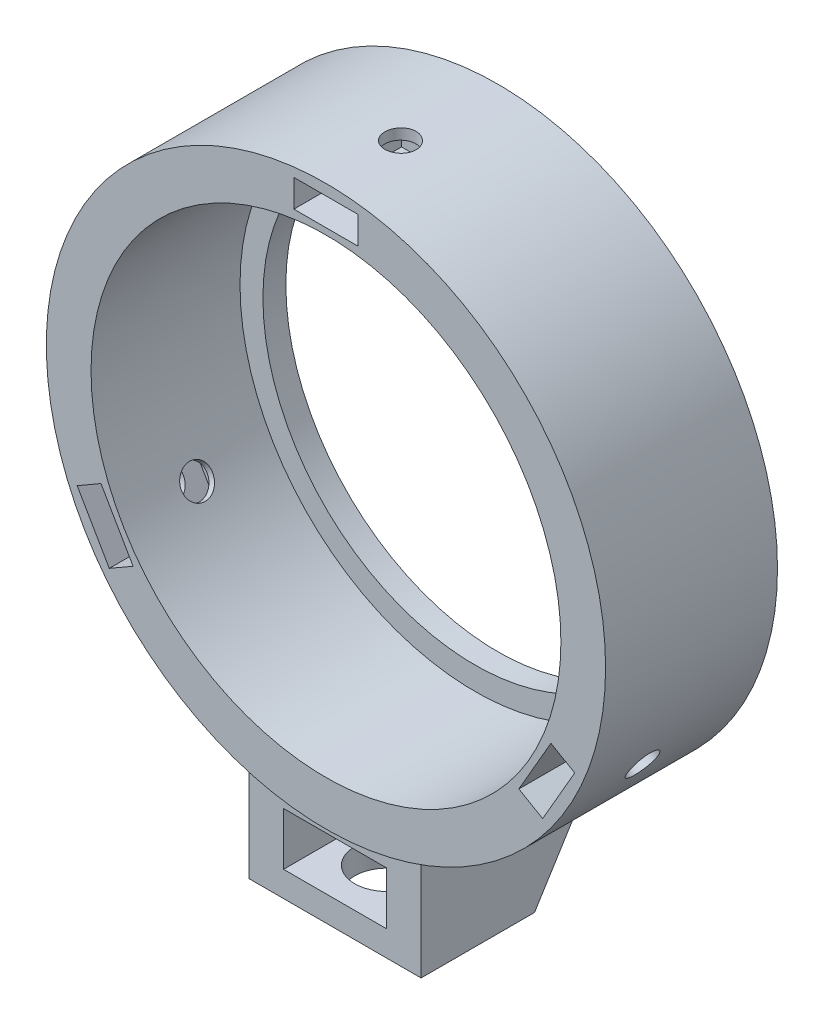
SolidWorks part; units mm, degrees
ref_plane "Front Plane" through (0, 0, 0) normal (0, 0, 1) x (1, 0, 0)
ref_plane "Top Plane" through (0, 0, 0) normal (0, 1, 0) x (1, 0, 0)
ref_plane "Right Plane" through (0, 0, 0) normal (1, 0, 0) x (0, 0, -1)
sketch "Sketch1" plane through (0, 0, 0) normal (0, 0, 1) x (1, 0, 0)
  circle A0 centre (0, 0) radius 30.988
  dimension "D1" = 61.976
extrude "Boss-Extrude1" add sketch "Sketch1" along normal blind 19.05
sketch "Sketch2" plane through (0, 0, 19.05) normal (0, 0, 1) x (1, 0, 0)
  circle A0 centre (0, 0) radius 26.035
  dimension "D1" = 52.07
extrude "Cut-Extrude1" cut sketch "Sketch2" against normal through all
sketch "Sketch4" plane through (0, 0, 0) normal (0, 0, -1) x (-1, 0, 0)
  circle A0 centre (0, 0) radius 26.035
  circle A1 centre (0, 0) radius 23.495
  circle A2 centre (0, 0) radius 26.035 construction
  dimension "D1" = 2.54
  dimension "D2" = 0
extrude "Boss-Extrude2" add sketch "Sketch4" against normal blind 2.54
sketch "Sketch11" plane through (0, 0, 19.05) normal (0, 0, 1) x (1, 0, 0)
  line L1 (-3.556, 26.7335) -> (3.556, 26.7335)
  line L2 (-3.556, 26.7335) -> (-3.556, 29.7815)
  line L3 (-3.556, 29.7815) -> (3.556, 29.7815)
  line L4 (3.556, 26.7335) -> (3.556, 29.7815)
  line L5 (-3.556, 26.7335) -> (3.556, 29.7815) construction
  line L6 (-3.556, 29.7815) -> (3.556, 26.7335) construction
  point P0 (0, 28.2575)
  dimension "D1" = 3.048
  dimension "D2" = 7.112
  dimension "D3" = 28.2575
extrude "Cut-Extrude3" cut sketch "Sketch11" against normal blind 11.938
pattern_circular "CirPattern2" count 3 over 360 about axis through (0, 0, 19.05) along (0, 0, -1) of "Cut-Extrude3"
ref_plane "Plane5" through (0, 12.7, 0) normal (0, 1, 0) x (1, 0, 0)
hole_wizard "#4 Clearance Hole1" positions "Sketch13" profile "Sketch14" hole size "#4" standard "ANSI Inch" end condition through all
sketch "Sketch13" plane through (0, 12.7, 0) normal (0, 1, 0) x (1, 0, 0)
  line L0 (3.556, -19.05) -> (-3.556, -19.05) construction
  point P0 (0, -10.795)
  dimension "D1" = 8.255
sketch "Sketch14" plane through (0, 12.7, 10.795) normal (1, 0, 0) x (0, 0, -1)
  line L0 (0, 0) -> (0, 34.4564)
  line L1 (0, 34.4564) -> (1.7272, 34.4564)
  line L2 (1.7272, 34.4564) -> (1.7272, 0)
  line L5 (1.7272, 0) -> (0, 0)
  line L11 (0, -6.35) -> (0, 107.95) construction
  dimension "Thru Hole Dia." = 3.4544
  dimension "Thru Hole Depth" = 34.4564
ref_plane "Plane6" through (0, -27.94, 0) normal (0, 1, 0) x (1, 0, 0)
sketch "Sketch15" plane through (0, -27.94, 0) normal (0, 1, 0) x (1, 0, 0)
  line L0 (-30.988, -19.05) -> (30.988, -19.05) construction
  line L1 (-9.144, -0.762) -> (9.906, -0.762)
  line L2 (-9.144, -0.762) -> (-9.144, -18.415)
  line L3 (-9.144, -18.415) -> (9.906, -18.415)
  line L4 (9.906, -0.762) -> (9.906, -18.415)
  line L5 (3.556, -7.112) -> (3.556, -19.05) construction
  line L6 (-3.556, -7.112) -> (-3.556, -19.05) construction
  line L8 (30.988, 0) -> (-30.988, 0) construction
  dimension "D1" = 19.05
  dimension "D2" = 0.762
  dimension "D3" = 0.635
  dimension "D4" = 6.35
  dimension "D5" = 5.588
extrude "Boss-Extrude3" add sketch "Sketch15" against normal blind 12.7
pattern_circular "CirPattern3" count 3 over 360 about axis through (0, 0, 19.05) along (0, 0, 1) of "#4 Clearance Hole1"
sketch "Sketch16" plane through (0, 0, 18.415) normal (0, 0, 1) x (1, 0, 0)
  line L0 (-9.144, -40.64) -> (-9.144, -29.6082) construction
  line L1 (-5.334, -31.9867) -> (6.096, -31.9867)
  line L2 (-5.334, -31.9867) -> (-5.334, -37.8287)
  line L3 (-5.334, -37.8287) -> (6.096, -37.8287)
  line L4 (6.096, -31.9867) -> (6.096, -37.8287)
  line L5 (9.906, -40.64) -> (9.906, -29.362) construction
  dimension "D1" = 11.43
  dimension "D2" = 3.81
  dimension "D3" = 5.842
  dimension "D4" = 3.81
extrude "Cut-Extrude4" cut sketch "Sketch16" against normal through all
chamfer "Chamfer2" distance 5.08 angle 58 1 edges at (0.381, -40.64, 0.762) first distance on face at (0.381, -40.64, 9.5885)
sketch "Sketch20" plane through (0, 0, 2.54) normal (0, 0, 1) x (1, 0, 0)
  circle A0 centre (0, 0) radius 26.035
hole_wizard "1/4 Clearance Hole1" positions "Sketch25" profile "Sketch23" hole size "1/4" standard "ANSI Inch" end condition up to next
sketch "Sketch25" plane through (0, -40.64, 0) normal (0, -1, 0) x (-1, 0, 0)
  point P0 (0, -12.2895)
sketch "Sketch23" plane through (0, -40.64, 12.2895) normal (1, 0, 0) x (0, 0, -1)
  line L0 (0, 0) -> (0, 2.8113)
  line L1 (0, 2.8113) -> (3.5712, 2.8113)
  line L2 (3.5712, 2.8113) -> (3.5712, 0)
  line L5 (3.5712, 0) -> (0, 0)
  line L11 (0, -6.35) -> (0, 107.95) construction
  dimension "Thru Hole Dia." = 7.1425
  dimension "Thru Hole Depth" = 2.8113
